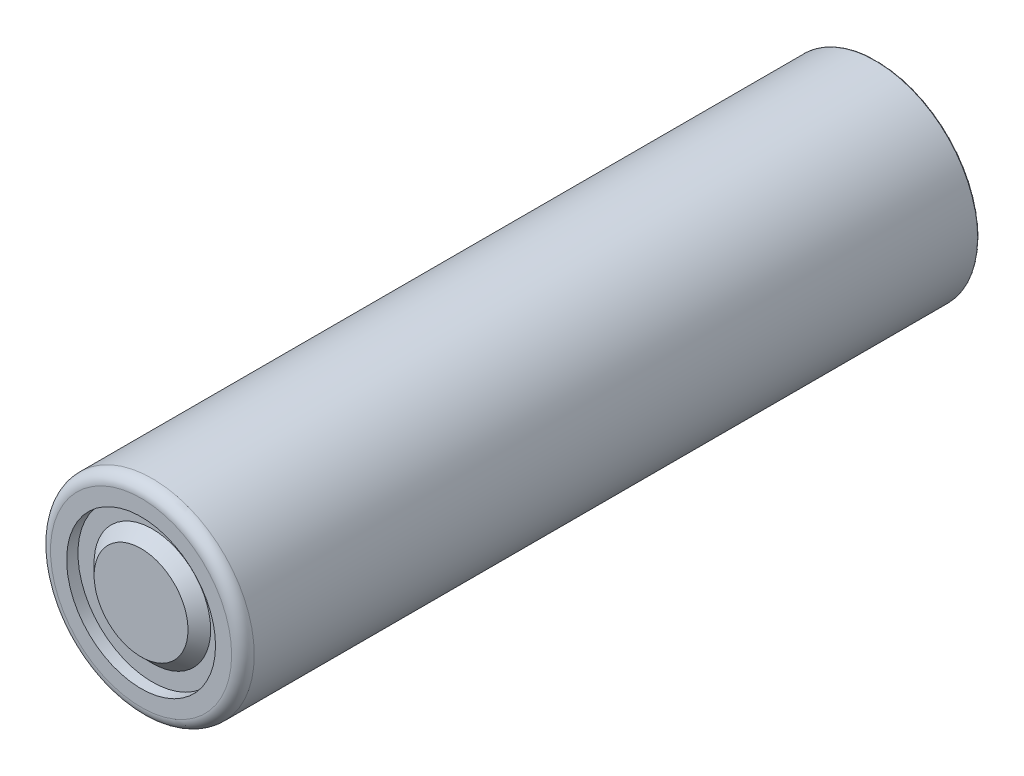
SolidWorks part; units mm, degrees
ref_plane "Front Plane" through (0, 0, 0) normal (0, 0, 1) x (1, 0, 0)
ref_plane "Top Plane" through (0, 0, 0) normal (0, 1, 0) x (1, 0, 0)
ref_plane "Right Plane" through (0, 0, 0) normal (1, 0, 0) x (0, 0, -1)
sketch "Sketch1" plane through (0, 0, 0) normal (0, 0, 1) x (1, 0, 0)
  circle A0 centre (0, 0) radius 9
  dimension "D1" = 18
extrude "Boss-Extrude1" add sketch "Sketch1" along normal blind 65
sketch "Sketch2" plane through (0, 0, 65) normal (0, 0, 1) x (1, 0, 0)
  circle A0 centre (0, 0) radius 6.5765
  circle A1 centre (0, 0) radius 5.1467
extrude "Cut-Extrude2" cut sketch "Sketch2" against normal blind 1
fillet "Fillet1" radius 1 1 edges at (9, 0, 65)
chamfer "Chamfer1" distance 1 angle 45 1 edges at (5.1467, 0, 65)
sketch "Sketch3" plane through (0, 0, 0) normal (0, 0, -1) x (-1, 0, 0)
  circle A0 centre (0, 0) radius 8.2463
  circle A1 centre (0, 0) radius 7.7867
extrude "Cut-Extrude3" cut sketch "Sketch3" against normal blind 0.4
fillet "Fillet2" radius 0.1 1 edges at (9, 0, 0)
